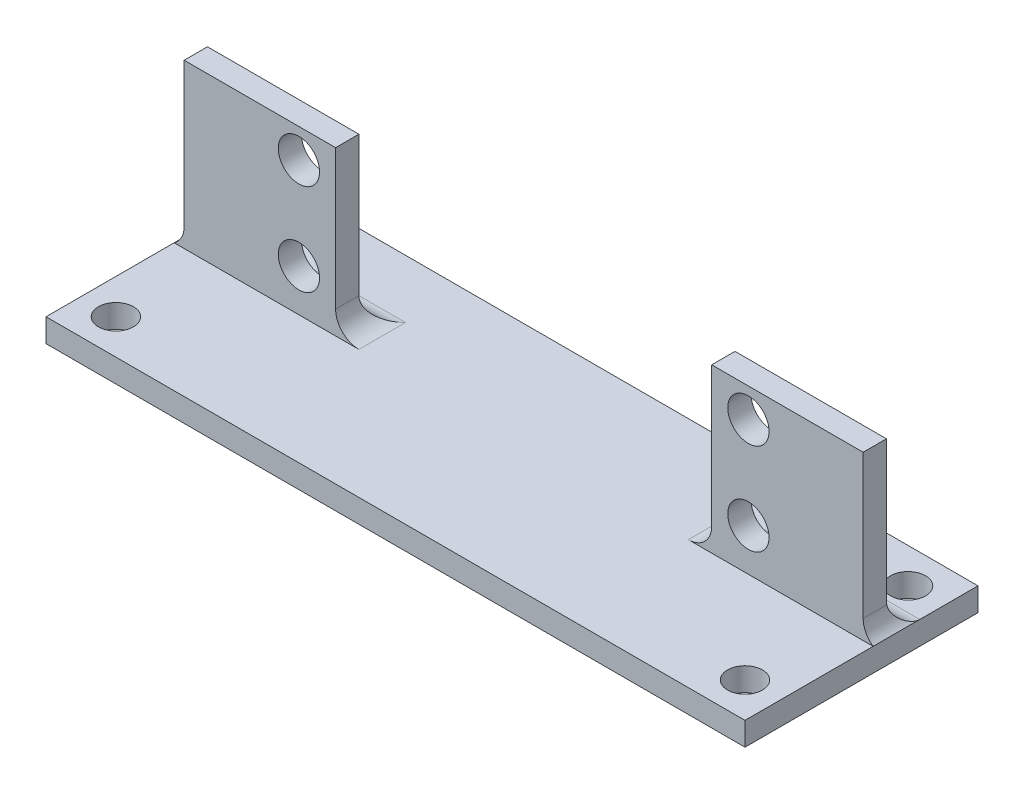
SolidWorks part; units mm, degrees
ref_plane "Front Plane" through (0, 0, 0) normal (0, 0, 1) x (1, 0, 0)
ref_plane "Top Plane" through (0, 0, 0) normal (0, 1, 0) x (1, 0, 0)
ref_plane "Right Plane" through (0, 0, 0) normal (1, 0, 0) x (0, 0, -1)
sketch "Sketch1" plane through (0, 0, 0) normal (0, 1, 0) x (1, 0, 0)
  line L1 (-38.1, 12.7) -> (38.1, 12.7)
  line L2 (-38.1, 12.7) -> (-38.1, -12.7)
  line L3 (-38.1, -12.7) -> (38.1, -12.7)
  line L4 (38.1, 12.7) -> (38.1, -12.7)
  line L5 (-38.1, 12.7) -> (38.1, -12.7) construction
  line L6 (-38.1, -12.7) -> (38.1, 12.7) construction
  circle A0 centre (-34.29, 8.89) radius 1.905
  circle A1 centre (-34.29, -8.89) radius 1.905
  circle A2 centre (34.29, 8.89) radius 1.905
  circle A3 centre (34.29, -8.89) radius 1.905
  point P0 (0, 0)
  dimension "D3" = 3.81
  dimension "D6" = 3.81
  dimension "D1" = 76.2
  dimension "D2" = 25.4
  dimension "D4" = 3.81
  dimension "D5" = 3.81
  dimension "D7" = 3.81
extrude "Boss-Extrude1" add sketch "Sketch1" along normal blind 2.54
sketch "Sketch2" plane through (0, 2.54, 0) normal (0, 1, 0) x (1, 0, 0)
  line L0 (-20.5, 2.54) -> (20.5, 2.54) construction
  line L1 (-37.01, 3.81) -> (-20.5, 3.81)
  line L2 (-37.01, 3.81) -> (-37.01, 1.27)
  line L3 (-37.01, 1.27) -> (-20.5, 1.27)
  line L4 (-20.5, 3.81) -> (-20.5, 1.27)
  line L5 (20.5, 3.81) -> (37.01, 3.81)
  line L6 (20.5, 3.81) -> (20.5, 1.27)
  line L7 (20.5, 1.27) -> (37.01, 1.27)
  line L8 (37.01, 3.81) -> (37.01, 1.27)
  point P10 (0, 2.54)
  dimension "D1" = 16.51
  dimension "D2" = 2.54
  dimension "D3" = 41
  dimension "D4" = 2.54
extrude "Boss-Extrude2" add sketch "Sketch2" along normal blind 17.78
sketch "Sketch3" plane through (0, 0, -1.27) normal (0, 0, 1) x (1, 0, 0)
  line L0 (-24.5, 17.14) -> (24.5, 17.14) construction
  line L1 (-37.01, 2.54) -> (-20.5, 2.54) construction
  circle A0 centre (-24.5, 17.14) radius 2.25
  circle A1 centre (24.5, 17.14) radius 2.25
  circle A2 centre (-24.5, 7.14) radius 2.25
  circle A3 centre (24.5, 7.14) radius 2.25
  point P8 (0, 17.14)
  dimension "D2" = 4.5
  dimension "D1" = 49
  dimension "D3" = 10
  dimension "D4" = 4.6
extrude "Cut-Extrude1" cut sketch "Sketch3" against normal through all
fillet "Fillet1" radius 2.54 6 edges at (-20.5, 2.54, -2.54) (-28.755, 2.54, -3.81) (-37.01, 2.54, -2.54) (37.01, 2.54, -2.54) (20.5, 2.54, -2.54) (28.755, 2.54, -3.81)
